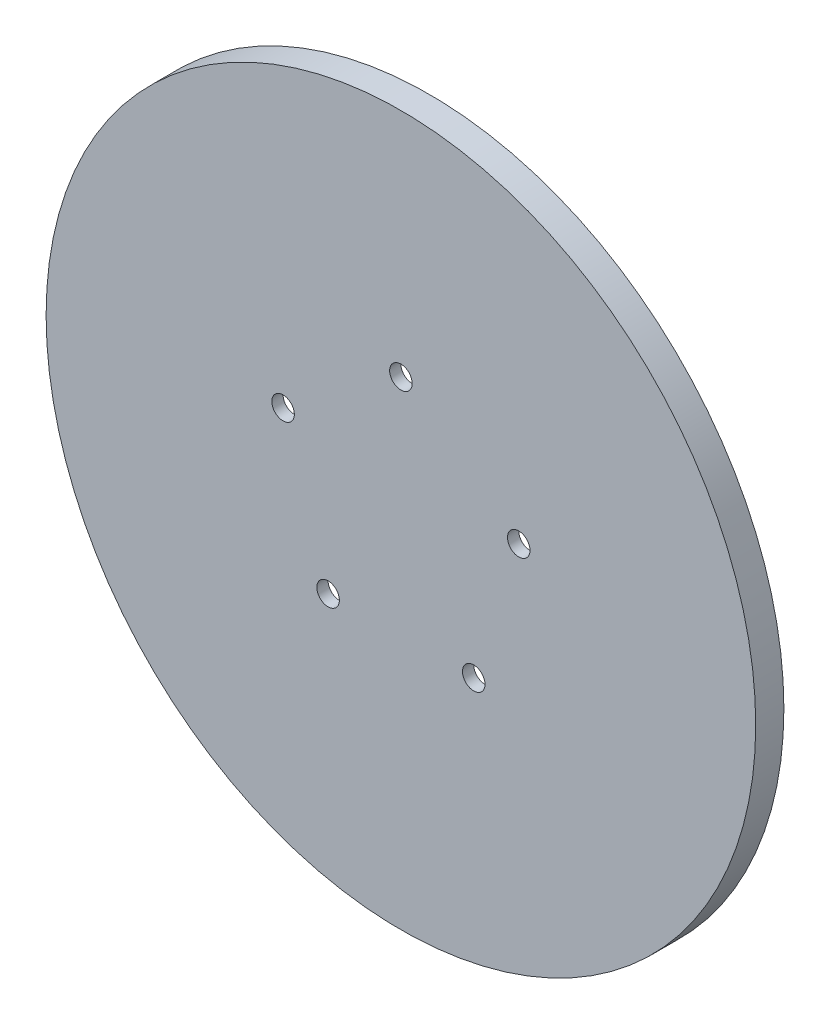
SolidWorks part; units mm, degrees
material "AISI 1045 Steel, cold drawn"
ref_plane "Front Plane" through (0, 0, 0) normal (0, 0, 1) x (1, 0, 0)
ref_plane "Top Plane" through (0, 0, 0) normal (0, 1, 0) x (1, 0, 0)
ref_plane "Right Plane" through (0, 0, 0) normal (1, 0, 0) x (0, 0, -1)
sketch "Sketch1" plane through (0, 0, 0) normal (0, 0, 1) x (1, 0, 0)
  line L0 (0, 0) -> (-4.5942, 70.0933) construction
  line L1 (0, 0) -> (4.5942, 70.0933) construction
  line L2 (0, 0) -> (0, 75.4253) construction
  line L3 (-0.762, 75.4215) -> (0.762, 75.4215)
  line L4 (0.762, 75.4215) -> (1.457, 73.512)
  line L5 (9.089, 74.8757) -> (8.1507, 73.0733)
  line L6 (18.7845, 73.0487) -> (17.619, 71.3842)
  line L7 (10.6, 74.6767) -> (11.0398, 72.6929)
  line L8 (9.089, 74.8757) -> (10.6, 74.6767)
  line L9 (28.1585, 69.9719) -> (26.7857, 68.4738)
  line L10 (20.2565, 72.6543) -> (20.4336, 70.63)
  line L11 (18.7845, 73.0487) -> (20.2565, 72.6543)
  line L12 (37.0508, 65.6979) -> (35.4942, 64.3917)
  line L13 (29.5665, 69.3887) -> (29.4779, 67.3587)
  line L14 (28.1585, 69.9719) -> (29.5665, 69.3887)
  line L15 (45.3091, 60.2997) -> (43.5954, 59.2079)
  line L16 (38.3706, 64.9359) -> (38.0178, 62.9348)
  line L17 (37.0508, 65.6979) -> (38.3706, 64.9359)
  line L18 (52.7922, 53.8698) -> (50.9506, 53.0111)
  line L19 (46.5182, 59.372) -> (45.9072, 57.434)
  line L20 (45.3091, 60.2997) -> (46.5182, 59.372)
  line L21 (59.372, 46.5182) -> (57.434, 45.9072)
  line L22 (53.8698, 52.7922) -> (53.0111, 50.9506)
  line L23 (52.7922, 53.8698) -> (53.8698, 52.7922)
  line L24 (64.9359, 38.3706) -> (62.9348, 38.0178)
  line L25 (60.2997, 45.3091) -> (59.2079, 43.5954)
  line L26 (59.372, 46.5182) -> (60.2997, 45.3091)
  line L27 (69.3887, 29.5665) -> (67.3587, 29.4779)
  line L28 (65.6979, 37.0508) -> (64.3917, 35.4942)
  line L29 (64.9359, 38.3706) -> (65.6979, 37.0508)
  line L30 (72.6543, 20.2565) -> (70.63, 20.4336)
  line L31 (69.9719, 28.1585) -> (68.4738, 26.7857)
  line L32 (69.3887, 29.5665) -> (69.9719, 28.1585)
  line L33 (74.6767, 10.6) -> (72.6929, 11.0398)
  line L34 (73.0487, 18.7845) -> (71.3842, 17.619)
  line L35 (72.6543, 20.2565) -> (73.0487, 18.7845)
  line L36 (75.4215, 0.762) -> (73.512, 1.457)
  line L37 (74.8757, 9.089) -> (73.0733, 8.1507)
  line L38 (74.6767, 10.6) -> (74.8757, 9.089)
  line L39 (74.8757, -9.089) -> (73.0733, -8.1507)
  line L40 (75.4215, -0.762) -> (73.512, -1.457)
  line L41 (75.4215, 0.762) -> (75.4215, -0.762)
  line L42 (73.0487, -18.7845) -> (71.3842, -17.619)
  line L43 (74.6767, -10.6) -> (72.6929, -11.0398)
  line L44 (74.8757, -9.089) -> (74.6767, -10.6)
  line L45 (69.9719, -28.1585) -> (68.4738, -26.7857)
  line L46 (72.6543, -20.2565) -> (70.63, -20.4336)
  line L47 (73.0487, -18.7845) -> (72.6543, -20.2565)
  line L48 (65.6979, -37.0508) -> (64.3917, -35.4942)
  line L49 (69.3887, -29.5665) -> (67.3587, -29.4779)
  line L50 (69.9719, -28.1585) -> (69.3887, -29.5665)
  line L51 (60.2997, -45.3091) -> (59.2079, -43.5954)
  line L52 (64.9359, -38.3706) -> (62.9348, -38.0178)
  line L53 (65.6979, -37.0508) -> (64.9359, -38.3706)
  line L54 (53.8698, -52.7922) -> (53.0111, -50.9506)
  line L55 (59.372, -46.5182) -> (57.434, -45.9072)
  line L56 (60.2997, -45.3091) -> (59.372, -46.5182)
  line L57 (46.5182, -59.372) -> (45.9072, -57.434)
  line L58 (52.7922, -53.8698) -> (50.9506, -53.0111)
  line L59 (53.8698, -52.7922) -> (52.7922, -53.8698)
  line L60 (38.3706, -64.9359) -> (38.0178, -62.9348)
  line L61 (45.3091, -60.2997) -> (43.5954, -59.2079)
  line L62 (46.5182, -59.372) -> (45.3091, -60.2997)
  line L63 (29.5665, -69.3887) -> (29.4779, -67.3587)
  line L64 (37.0508, -65.6979) -> (35.4942, -64.3917)
  line L65 (38.3706, -64.9359) -> (37.0508, -65.6979)
  line L66 (20.2565, -72.6543) -> (20.4336, -70.63)
  line L67 (28.1585, -69.9719) -> (26.7857, -68.4738)
  line L68 (29.5665, -69.3887) -> (28.1585, -69.9719)
  line L69 (10.6, -74.6767) -> (11.0398, -72.6929)
  line L70 (18.7845, -73.0487) -> (17.619, -71.3842)
  line L71 (20.2565, -72.6543) -> (18.7845, -73.0487)
  line L72 (0.762, -75.4215) -> (1.457, -73.512)
  line L73 (9.089, -74.8757) -> (8.1507, -73.0733)
  line L74 (10.6, -74.6767) -> (9.089, -74.8757)
  line L75 (-9.089, -74.8757) -> (-8.1507, -73.0733)
  line L76 (-0.762, -75.4215) -> (-1.457, -73.512)
  line L77 (0.762, -75.4215) -> (-0.762, -75.4215)
  line L78 (-18.7845, -73.0487) -> (-17.619, -71.3842)
  line L79 (-10.6, -74.6767) -> (-11.0398, -72.6929)
  line L80 (-9.089, -74.8757) -> (-10.6, -74.6767)
  line L81 (-28.1585, -69.9719) -> (-26.7857, -68.4738)
  line L82 (-20.2565, -72.6543) -> (-20.4336, -70.63)
  line L83 (-18.7845, -73.0487) -> (-20.2565, -72.6543)
  line L84 (-37.0508, -65.6979) -> (-35.4942, -64.3917)
  line L85 (-29.5665, -69.3887) -> (-29.4779, -67.3587)
  line L86 (-28.1585, -69.9719) -> (-29.5665, -69.3887)
  line L87 (-45.3091, -60.2997) -> (-43.5954, -59.2079)
  line L88 (-38.3706, -64.9359) -> (-38.0178, -62.9348)
  line L89 (-37.0508, -65.6979) -> (-38.3706, -64.9359)
  line L90 (-52.7922, -53.8698) -> (-50.9506, -53.0111)
  line L91 (-46.5182, -59.372) -> (-45.9072, -57.434)
  line L92 (-45.3091, -60.2997) -> (-46.5182, -59.372)
  line L93 (-59.372, -46.5182) -> (-57.434, -45.9072)
  line L94 (-53.8698, -52.7922) -> (-53.0111, -50.9506)
  line L95 (-52.7922, -53.8698) -> (-53.8698, -52.7922)
  line L96 (-64.9359, -38.3706) -> (-62.9348, -38.0178)
  line L97 (-60.2997, -45.3091) -> (-59.2079, -43.5954)
  line L98 (-59.372, -46.5182) -> (-60.2997, -45.3091)
  line L99 (-69.3887, -29.5665) -> (-67.3587, -29.4779)
  line L100 (-65.6979, -37.0508) -> (-64.3917, -35.4942)
  line L101 (-64.9359, -38.3706) -> (-65.6979, -37.0508)
  line L102 (-72.6543, -20.2565) -> (-70.63, -20.4336)
  line L103 (-69.9719, -28.1585) -> (-68.4738, -26.7857)
  line L104 (-69.3887, -29.5665) -> (-69.9719, -28.1585)
  line L105 (-74.6767, -10.6) -> (-72.6929, -11.0398)
  line L106 (-73.0487, -18.7845) -> (-71.3842, -17.619)
  line L107 (-72.6543, -20.2565) -> (-73.0487, -18.7845)
  line L108 (-75.4215, -0.762) -> (-73.512, -1.457)
  line L109 (-74.8757, -9.089) -> (-73.0733, -8.1507)
  line L110 (-74.6767, -10.6) -> (-74.8757, -9.089)
  line L111 (-74.8757, 9.089) -> (-73.0733, 8.1507)
  line L112 (-75.4215, 0.762) -> (-73.512, 1.457)
  line L113 (-75.4215, -0.762) -> (-75.4215, 0.762)
  line L114 (-73.0487, 18.7845) -> (-71.3842, 17.619)
  line L115 (-74.6767, 10.6) -> (-72.6929, 11.0398)
  line L116 (-74.8757, 9.089) -> (-74.6767, 10.6)
  line L117 (-69.9719, 28.1585) -> (-68.4738, 26.7857)
  line L118 (-72.6543, 20.2565) -> (-70.63, 20.4336)
  line L119 (-73.0487, 18.7845) -> (-72.6543, 20.2565)
  line L120 (-65.6979, 37.0508) -> (-64.3917, 35.4942)
  line L121 (-69.3887, 29.5665) -> (-67.3587, 29.4779)
  line L122 (-69.9719, 28.1585) -> (-69.3887, 29.5665)
  line L123 (-60.2997, 45.3091) -> (-59.2079, 43.5954)
  line L124 (-64.9359, 38.3706) -> (-62.9348, 38.0178)
  line L125 (-65.6979, 37.0508) -> (-64.9359, 38.3706)
  line L126 (-53.8698, 52.7922) -> (-53.0111, 50.9506)
  line L127 (-59.372, 46.5182) -> (-57.434, 45.9072)
  line L128 (-60.2997, 45.3091) -> (-59.372, 46.5182)
  line L129 (-46.5182, 59.372) -> (-45.9072, 57.434)
  line L130 (-52.7922, 53.8698) -> (-50.9506, 53.0111)
  line L131 (-53.8698, 52.7922) -> (-52.7922, 53.8698)
  line L132 (-38.3706, 64.9359) -> (-38.0178, 62.9348)
  line L133 (-45.3091, 60.2997) -> (-43.5954, 59.2079)
  line L134 (-46.5182, 59.372) -> (-45.3091, 60.2997)
  line L135 (-29.5665, 69.3887) -> (-29.4779, 67.3587)
  line L136 (-37.0508, 65.6979) -> (-35.4942, 64.3917)
  line L137 (-38.3706, 64.9359) -> (-37.0508, 65.6979)
  line L138 (-20.2565, 72.6543) -> (-20.4336, 70.63)
  line L139 (-28.1585, 69.9719) -> (-26.7857, 68.4738)
  line L140 (-29.5665, 69.3887) -> (-28.1585, 69.9719)
  line L141 (-10.6, 74.6767) -> (-11.0398, 72.6929)
  line L142 (-18.7845, 73.0487) -> (-17.619, 71.3842)
  line L143 (-20.2565, 72.6543) -> (-18.7845, 73.0487)
  line L144 (-0.762, 75.4215) -> (-1.457, 73.512)
  line L145 (-9.089, 74.8757) -> (-8.1507, 73.0733)
  line L146 (-10.6, 74.6767) -> (-9.089, 74.8757)
  circle A0 centre (0, 0) radius 75.4253 construction
  circle A1 centre (0, 0) radius 70.2437 construction
  circle A2 centre (0, 0) radius 7.9375
  circle A3 centre (0, 0) radius 73.5264 construction
  arc A4 (1.457, 73.512) -> (4.5942, 70.0933) centre (4.8137, 73.4436) ccw
  arc A5 (4.5942, 70.0933) -> (8.1507, 73.0733) centre (4.8137, 73.4436) ccw
  arc A6 (13.7039, 68.894) -> (17.619, 71.3842) centre (14.3589, 72.1869) ccw
  arc A7 (11.0398, 72.6929) -> (13.7039, 68.894) centre (14.3589, 72.1869) ccw
  arc A8 (22.5791, 66.5159) -> (26.7857, 68.4738) centre (23.6583, 69.6952) ccw
  arc A9 (20.4336, 70.63) -> (22.5791, 66.5159) centre (23.6583, 69.6952) ccw
  arc A10 (31.068, 62.9997) -> (35.4942, 64.3917) centre (32.553, 66.0109) ccw
  arc A11 (29.4779, 67.3587) -> (31.068, 62.9997) centre (32.553, 66.0109) ccw
  arc A12 (39.0253, 58.4055) -> (43.5954, 59.2079) centre (40.8906, 61.1971) ccw
  arc A13 (38.0178, 62.9348) -> (39.0253, 58.4055) centre (40.8906, 61.1971) ccw
  arc A14 (46.3149, 52.812) -> (50.9506, 53.0111) centre (48.5286, 55.3363) ccw
  arc A15 (45.9072, 57.434) -> (46.3149, 52.812) centre (48.5286, 55.3363) ccw
  arc A16 (52.812, 46.3149) -> (57.434, 45.9072) centre (55.3363, 48.5286) ccw
  arc A17 (53.0111, 50.9506) -> (52.812, 46.3149) centre (55.3363, 48.5286) ccw
  arc A18 (58.4055, 39.0253) -> (62.9348, 38.0178) centre (61.1971, 40.8906) ccw
  arc A19 (59.2079, 43.5954) -> (58.4055, 39.0253) centre (61.1971, 40.8906) ccw
  arc A20 (62.9997, 31.068) -> (67.3587, 29.4779) centre (66.0109, 32.553) ccw
  arc A21 (64.3917, 35.4942) -> (62.9997, 31.068) centre (66.0109, 32.553) ccw
  arc A22 (66.5159, 22.5791) -> (70.63, 20.4336) centre (69.6952, 23.6583) ccw
  arc A23 (68.4738, 26.7857) -> (66.5159, 22.5791) centre (69.6952, 23.6583) ccw
  arc A24 (68.894, 13.7039) -> (72.6929, 11.0398) centre (72.1869, 14.3589) ccw
  arc A25 (71.3842, 17.619) -> (68.894, 13.7039) centre (72.1869, 14.3589) ccw
  arc A26 (70.0933, 4.5942) -> (73.512, 1.457) centre (73.4436, 4.8137) ccw
  arc A27 (73.0733, 8.1507) -> (70.0933, 4.5942) centre (73.4436, 4.8137) ccw
  arc A28 (70.0933, -4.5942) -> (73.0733, -8.1507) centre (73.4436, -4.8137) ccw
  arc A29 (73.512, -1.457) -> (70.0933, -4.5942) centre (73.4436, -4.8137) ccw
  arc A30 (68.894, -13.7039) -> (71.3842, -17.619) centre (72.1869, -14.3589) ccw
  arc A31 (72.6929, -11.0398) -> (68.894, -13.7039) centre (72.1869, -14.3589) ccw
  arc A32 (66.5159, -22.5791) -> (68.4738, -26.7857) centre (69.6952, -23.6583) ccw
  arc A33 (70.63, -20.4336) -> (66.5159, -22.5791) centre (69.6952, -23.6583) ccw
  arc A34 (62.9997, -31.068) -> (64.3917, -35.4942) centre (66.0109, -32.553) ccw
  arc A35 (67.3587, -29.4779) -> (62.9997, -31.068) centre (66.0109, -32.553) ccw
  arc A36 (58.4055, -39.0253) -> (59.2079, -43.5954) centre (61.1971, -40.8906) ccw
  arc A37 (62.9348, -38.0178) -> (58.4055, -39.0253) centre (61.1971, -40.8906) ccw
  arc A38 (52.812, -46.3149) -> (53.0111, -50.9506) centre (55.3363, -48.5286) ccw
  arc A39 (57.434, -45.9072) -> (52.812, -46.3149) centre (55.3363, -48.5286) ccw
  arc A40 (46.3149, -52.812) -> (45.9072, -57.434) centre (48.5286, -55.3363) ccw
  arc A41 (50.9506, -53.0111) -> (46.3149, -52.812) centre (48.5286, -55.3363) ccw
  arc A42 (39.0253, -58.4055) -> (38.0178, -62.9348) centre (40.8906, -61.1971) ccw
  arc A43 (43.5954, -59.2079) -> (39.0253, -58.4055) centre (40.8906, -61.1971) ccw
  arc A44 (31.068, -62.9997) -> (29.4779, -67.3587) centre (32.553, -66.0109) ccw
  arc A45 (35.4942, -64.3917) -> (31.068, -62.9997) centre (32.553, -66.0109) ccw
  arc A46 (22.5791, -66.5159) -> (20.4336, -70.63) centre (23.6583, -69.6952) ccw
  arc A47 (26.7857, -68.4738) -> (22.5791, -66.5159) centre (23.6583, -69.6952) ccw
  arc A48 (13.7039, -68.894) -> (11.0398, -72.6929) centre (14.3589, -72.1869) ccw
  arc A49 (17.619, -71.3842) -> (13.7039, -68.894) centre (14.3589, -72.1869) ccw
  arc A50 (4.5942, -70.0933) -> (1.457, -73.512) centre (4.8137, -73.4436) ccw
  arc A51 (8.1507, -73.0733) -> (4.5942, -70.0933) centre (4.8137, -73.4436) ccw
  arc A52 (-4.5942, -70.0933) -> (-8.1507, -73.0733) centre (-4.8137, -73.4436) ccw
  arc A53 (-1.457, -73.512) -> (-4.5942, -70.0933) centre (-4.8137, -73.4436) ccw
  arc A54 (-13.7039, -68.894) -> (-17.619, -71.3842) centre (-14.3589, -72.1869) ccw
  arc A55 (-11.0398, -72.6929) -> (-13.7039, -68.894) centre (-14.3589, -72.1869) ccw
  arc A56 (-22.5791, -66.5159) -> (-26.7857, -68.4738) centre (-23.6583, -69.6952) ccw
  arc A57 (-20.4336, -70.63) -> (-22.5791, -66.5159) centre (-23.6583, -69.6952) ccw
  arc A58 (-31.068, -62.9997) -> (-35.4942, -64.3917) centre (-32.553, -66.0109) ccw
  arc A59 (-29.4779, -67.3587) -> (-31.068, -62.9997) centre (-32.553, -66.0109) ccw
  arc A60 (-39.0253, -58.4055) -> (-43.5954, -59.2079) centre (-40.8906, -61.1971) ccw
  arc A61 (-38.0178, -62.9348) -> (-39.0253, -58.4055) centre (-40.8906, -61.1971) ccw
  arc A62 (-46.3149, -52.812) -> (-50.9506, -53.0111) centre (-48.5286, -55.3363) ccw
  arc A63 (-45.9072, -57.434) -> (-46.3149, -52.812) centre (-48.5286, -55.3363) ccw
  arc A64 (-52.812, -46.3149) -> (-57.434, -45.9072) centre (-55.3363, -48.5286) ccw
  arc A65 (-53.0111, -50.9506) -> (-52.812, -46.3149) centre (-55.3363, -48.5286) ccw
  arc A66 (-58.4055, -39.0253) -> (-62.9348, -38.0178) centre (-61.1971, -40.8906) ccw
  arc A67 (-59.2079, -43.5954) -> (-58.4055, -39.0253) centre (-61.1971, -40.8906) ccw
  arc A68 (-62.9997, -31.068) -> (-67.3587, -29.4779) centre (-66.0109, -32.553) ccw
  arc A69 (-64.3917, -35.4942) -> (-62.9997, -31.068) centre (-66.0109, -32.553) ccw
  arc A70 (-66.5159, -22.5791) -> (-70.63, -20.4336) centre (-69.6952, -23.6583) ccw
  arc A71 (-68.4738, -26.7857) -> (-66.5159, -22.5791) centre (-69.6952, -23.6583) ccw
  arc A72 (-68.894, -13.7039) -> (-72.6929, -11.0398) centre (-72.1869, -14.3589) ccw
  arc A73 (-71.3842, -17.619) -> (-68.894, -13.7039) centre (-72.1869, -14.3589) ccw
  arc A74 (-70.0933, -4.5942) -> (-73.512, -1.457) centre (-73.4436, -4.8137) ccw
  arc A75 (-73.0733, -8.1507) -> (-70.0933, -4.5942) centre (-73.4436, -4.8137) ccw
  arc A76 (-70.0933, 4.5942) -> (-73.0733, 8.1507) centre (-73.4436, 4.8137) ccw
  arc A77 (-73.512, 1.457) -> (-70.0933, 4.5942) centre (-73.4436, 4.8137) ccw
  arc A78 (-68.894, 13.7039) -> (-71.3842, 17.619) centre (-72.1869, 14.3589) ccw
  arc A79 (-72.6929, 11.0398) -> (-68.894, 13.7039) centre (-72.1869, 14.3589) ccw
  arc A80 (-66.5159, 22.5791) -> (-68.4738, 26.7857) centre (-69.6952, 23.6583) ccw
  arc A81 (-70.63, 20.4336) -> (-66.5159, 22.5791) centre (-69.6952, 23.6583) ccw
  arc A82 (-62.9997, 31.068) -> (-64.3917, 35.4942) centre (-66.0109, 32.553) ccw
  arc A83 (-67.3587, 29.4779) -> (-62.9997, 31.068) centre (-66.0109, 32.553) ccw
  arc A84 (-58.4055, 39.0253) -> (-59.2079, 43.5954) centre (-61.1971, 40.8906) ccw
  arc A85 (-62.9348, 38.0178) -> (-58.4055, 39.0253) centre (-61.1971, 40.8906) ccw
  arc A86 (-52.812, 46.3149) -> (-53.0111, 50.9506) centre (-55.3363, 48.5286) ccw
  arc A87 (-57.434, 45.9072) -> (-52.812, 46.3149) centre (-55.3363, 48.5286) ccw
  arc A88 (-46.3149, 52.812) -> (-45.9072, 57.434) centre (-48.5286, 55.3363) ccw
  arc A89 (-50.9506, 53.0111) -> (-46.3149, 52.812) centre (-48.5286, 55.3363) ccw
  arc A90 (-39.0253, 58.4055) -> (-38.0178, 62.9348) centre (-40.8906, 61.1971) ccw
  arc A91 (-43.5954, 59.2079) -> (-39.0253, 58.4055) centre (-40.8906, 61.1971) ccw
  arc A92 (-31.068, 62.9997) -> (-29.4779, 67.3587) centre (-32.553, 66.0109) ccw
  arc A93 (-35.4942, 64.3917) -> (-31.068, 62.9997) centre (-32.553, 66.0109) ccw
  arc A94 (-22.5791, 66.5159) -> (-20.4336, 70.63) centre (-23.6583, 69.6952) ccw
  arc A95 (-26.7857, 68.4738) -> (-22.5791, 66.5159) centre (-23.6583, 69.6952) ccw
  arc A96 (-13.7039, 68.894) -> (-11.0398, 72.6929) centre (-14.3589, 72.1869) ccw
  arc A97 (-17.619, 71.3842) -> (-13.7039, 68.894) centre (-14.3589, 72.1869) ccw
  arc A98 (-4.5942, 70.0933) -> (-1.457, 73.512) centre (-4.8137, 73.4436) ccw
  arc A99 (-8.1507, 73.0733) -> (-4.5942, 70.0933) centre (-4.8137, 73.4436) ccw
  point P11 (0, 75.4215)
  point P14 (0, 73.5264)
  dimension "D1" = 150.8506
  dimension "D2" = 140.4874
  dimension "D3" = 15.875
  dimension "D6" = 1.524
  dimension "D8" = 2.032
  dimension "D7" = 48
  dimension "D4" = 7.5
  dimension "D5" = 3.75
  dimension "D10" = 110
extrude "Boss-Extrude2" add sketch "Sketch1" along normal blind 4.0894 contours A99 L145 L146 L141 A96 A97 L142 L143 L138 A94 A95 L139 L140 L135 A92 A93 L136 L137 L132 A90 A91 L133 L134 L129 A88 A89 L130 L131 L126 A86 A87 L127 L128 L123 A84 A85 L124 L125 L120 A82 A83 L121 L122 L117 A80 A81 L118 L119 L114 A78 A79
sketch "Sketch3" plane through (0, 0, 0) normal (1, 0, 0) x (0, 0, -1)
  line L0 (-3.3274, 75.4215) -> (-3.8487, 73.4575)
  line L1 (-4.0894, 75.4215) -> (0, 75.4215) construction
  line L2 (-3.8487, 73.4575) -> (-4.0894, 70.63)
  line L6 (-2.0447, 75.4215) -> (-2.0447, 71.5759) construction
  line L11 (-3.3274, 75.4215) -> (-3.3274, 76.3648)
  line L12 (-3.3274, 76.3648) -> (-4.7523, 76.3648)
  line L13 (-4.7523, 76.3648) -> (-4.7523, 70.63)
  line L14 (-4.7523, 70.63) -> (-4.0894, 70.63)
  line L15 (0.6629, 70.63) -> (0, 70.63)
  line L16 (0.6629, 76.3648) -> (0.6629, 70.63)
  line L17 (-0.762, 76.3648) -> (0.6629, 76.3648)
  line L18 (-0.762, 75.4215) -> (-0.762, 76.3648)
  line L19 (-0.2407, 73.4575) -> (0, 70.63)
  line L20 (-0.762, 75.4215) -> (-0.2407, 73.4575)
  point P7 (-2.0447, 75.4215)
  dimension "D1" = 2.032
  dimension "D2" = 170
  dimension "D3" = 0.762
ref_axis "Axis1" through (0, 0, 4.0894) along (0, 0, -1)
revolve "Cut-Revolve3" cut sketch "Sketch3" angle 360 about axis through (0, 0, 4.0894) along (0, 0, -1)
ref_plane "Plane1" through (0, 0, 29.4894) normal (0, 0, 1) x (1, 0, 0)
sketch "Sketch4" plane through (0, 0, 29.4894) normal (0, 0, 1) x (1, 0, 0)
  circle A0 centre (0, 0) radius 75.4215
  circle A1 centre (0, 0) radius 80.01
  dimension "D1" = 160.02
extrude "Boss-Extrude3" add sketch "Sketch4" along normal blind 3.81 separate body
sketch "Sketch5" plane through (0, 0, 33.2994) normal (0, 0, 1) x (1, 0, 0)
  line L0 (-45.3057, 60.2975) -> (-43.5539, 59.1528)
  line L1 (-37.9827, 62.8754) -> (-38.3699, 64.9318)
  line L2 (60.2975, 45.3057) -> (59.1528, 43.5539)
  line L3 (62.8754, 37.9827) -> (64.9318, 38.3699)
  line L4 (45.3057, -60.2975) -> (43.5539, -59.1528)
  line L5 (37.9827, -62.8754) -> (38.3699, -64.9318)
  line L6 (-60.2975, -45.3057) -> (-59.1528, -43.5539)
  line L7 (-62.8754, -37.9827) -> (-64.9318, -38.3699)
  arc A0 (-43.5539, 59.1528) -> (-37.9827, 62.8754) centre (-40.8906, 61.1971) ccw
  arc A1 (-45.3057, 60.2975) -> (-38.3699, 64.9318) centre (0, 0) cw
  arc A2 (60.2975, 45.3057) -> (64.9318, 38.3699) centre (0, 0) cw
  arc A3 (59.1528, 43.5539) -> (62.8754, 37.9827) centre (61.1971, 40.8906) ccw
  arc A4 (45.3057, -60.2975) -> (38.3699, -64.9318) centre (0, 0) cw
  arc A5 (43.5539, -59.1528) -> (37.9827, -62.8754) centre (40.8906, -61.1971) ccw
  arc A6 (-60.2975, -45.3057) -> (-64.9318, -38.3699) centre (0, 0) cw
  arc A7 (-59.1528, -43.5539) -> (-62.8754, -37.9827) centre (-61.1971, -40.8906) ccw
  point P28 (0, 0)
  dimension "D1" = 4
extrude "Boss-Extrude5" add sketch "Sketch5" against normal blind 3.81
sketch "Sketch6" plane through (0, 0, 33.2994) normal (0, 0, 1) x (1, 0, 0)
  circle A0 centre (0, 0) radius 80.01
extrude "Boss-Extrude6" add sketch "Sketch6" along normal blind 2.54
sketch "Sketch8" plane through (0, 0, 33.2994) normal (0, 0, -1) x (-1, 0, 0)
  circle A0 centre (0, 0) radius 7.9375
extrude "Boss-Extrude7" add sketch "Sketch8" along normal blind 3.81
sketch "Sketch9" plane through (0, 0, 29.4894) normal (0, 0, -1) x (-1, 0, 0)
  circle A0 centre (0, 27.94) radius 2.54
  circle A1 centre (26.5725, 8.6339) radius 2.54
  circle A2 centre (16.4227, -22.6039) radius 2.54
  circle A3 centre (-16.4227, -22.6039) radius 2.54
  circle A4 centre (-26.5725, 8.6339) radius 2.54
  point P14 (0, 0)
  dimension "D1" = 5.08
  dimension "D2" = 27.94
  dimension "D3" = 5
extrude "Cut-Extrude2" cut sketch "Sketch9" against normal through all
delete or keep bodies "Body-Delete/Keep 1" type delete bodies bodies 105
